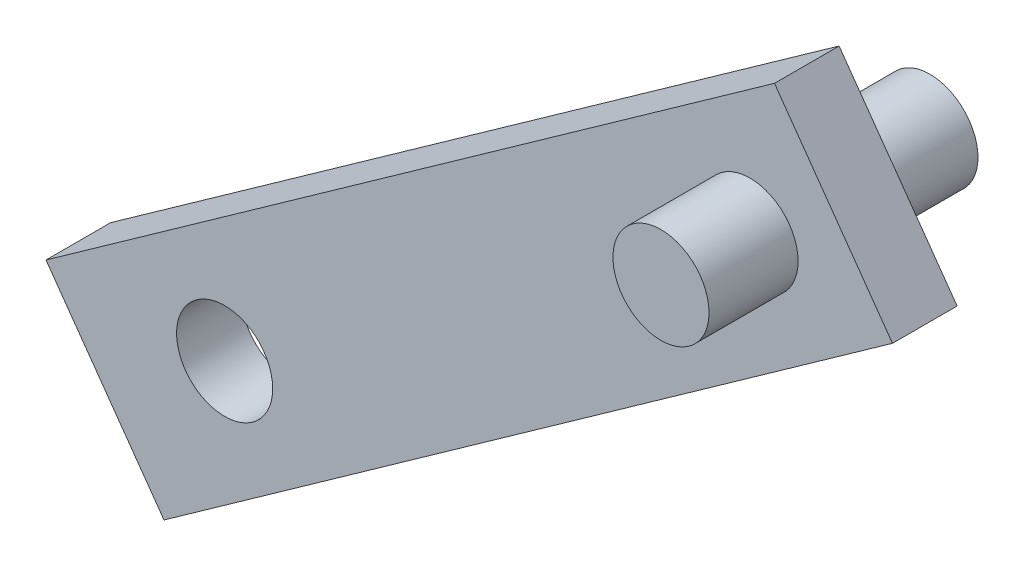
SolidWorks part; units mm, degrees
ref_plane "Front Plane" through (0, 0, 0) normal (0, 0, 1) x (1, 0, 0)
ref_plane "Top Plane" through (0, 0, 0) normal (0, 1, 0) x (1, 0, 0)
ref_plane "Right Plane" through (0, 0, 0) normal (1, 0, 0) x (0, 0, -1)
sketch "Sketch1" plane through (0, 0, 0) normal (0, 0, 1) x (1, 0, 0)
  line L0 (-36.4307, -6.3636) -> (-17.1697, 7.3117)
  line L1 (-36.4307, -6.3636) -> (-33.3109, -10.7577)
  line L2 (-33.3109, -10.7577) -> (-14.05, 2.9176)
  line L3 (-14.05, 2.9176) -> (-17.1697, 7.3117)
  line L4 (-33.2672, -4.1175) -> (-30.1474, -8.5115)
  line L5 (-34.8708, -8.5606) -> (-15.6098, 5.1147)
  line L6 (-19.3918, 5.734) -> (-16.2556, 1.3516)
  circle A0 centre (-31.7073, -6.3145) radius 1.27
  circle A1 centre (-17.8155, 3.5486) radius 1.27
  point P14 (-19.4105, 4.2133)
extrude "Boss-Extrude6" add sketch "Sketch1" along normal blind 1.7089 contours A1 L6 L0 L4 A0 L5 | A1 L5 A0 L4 L2 L6 | A1 L6 L2 L3 L5 | L5 A1 L6 | L6 A1 L5 | L5 A1 L6 | L6 A1 L5 | A1 L5 L3 L0 L6 | A0 L4 L0 L1 L5 | A0 L5 L1 L2 L4 region at (-34.291, -6.36, 0) region at (-25.5724, -0.2491, 0) region at (-32.6021, -8.7388, 0) region at (-17.4578, 5.6659, 0) region at (-17.6945, 4.2976, 0) region at (-18.5715, 3.6708, 0) region at (-23.9547, -2.5204, 0) region at (-15.6955, 3.1929, 0) region at (-17.9465, 2.7949, 0) region at (-17.0672, 3.4186, 0)
extrude "Boss-Extrude7" add sketch "Sketch1<8>" along normal blind 4.064 and the other way blind 3.048 contours L6 A1 L5 | L5 A1 L6 | L6 A1 L5 | L5 A1 L6 region at (-17.6945, 4.2976, 0) region at (-18.5715, 3.6708, 0) region at (-17.9465, 2.7949, 0) region at (-17.0672, 3.4186, 0)
sketch "Sketch1<8>" plane through (0, 0, 0) normal (0, 0, 1) x (1, 0, 0) same geometry as "Sketch1"
sketch "Sketch7" plane through (0, 0, 0) normal (0, 0, -1) x (-1, 0, 0)
